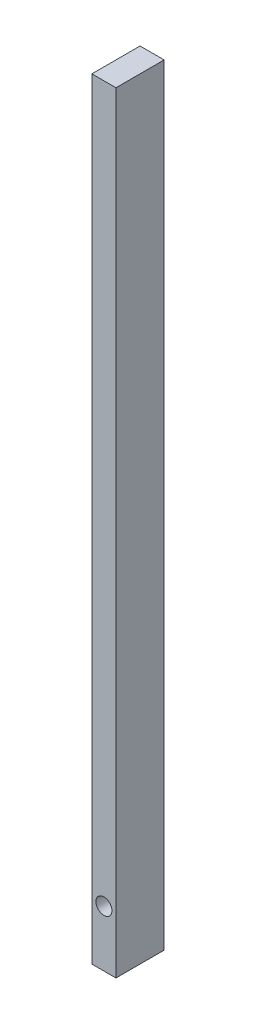
SolidWorks part; units mm, degrees
ref_plane "Front Plane" through (0, 0, 0) normal (0, 0, 1) x (1, 0, 0)
ref_plane "Top Plane" through (0, 0, 0) normal (0, 1, 0) x (1, 0, 0)
ref_plane "Right Plane" through (0, 0, 0) normal (1, 0, 0) x (0, 0, -1)
sketch "Sketch1" plane through (0, 0, 0) normal (1, 0, 0) x (0, 0, -1)
  line L1 (-19.05, 304.8) -> (19.05, 304.8)
  line L2 (-19.05, 304.8) -> (-19.05, -304.8)
  line L3 (-19.05, -304.8) -> (19.05, -304.8)
  line L4 (19.05, 304.8) -> (19.05, -304.8)
  line L5 (-19.05, 304.8) -> (19.05, -304.8) construction
  line L6 (-19.05, -304.8) -> (19.05, 304.8) construction
  point P0 (0, 0)
  dimension "D1" = 38.1
  dimension "D2" = 609.6
extrude "Boss-Extrude1" add sketch "Sketch1" along normal blind 19.05
sketch "Sketch2" plane through (0, 0, 19.05) normal (0, 0, 1) x (1, 0, 0)
  line L0 (9.525, -260.35) -> (9.525, -304.8) construction
  line L1 (19.05, -304.8) -> (0, -304.8) construction
  circle A0 centre (9.525, -260.35) radius 4.7625
  dimension "D2" = 9.525
  dimension "D1" = 44.45
extrude "Cut-Extrude1" cut sketch "Sketch2" against normal through all
sketch "Sketch3" plane through (0, 0, 19.05) normal (0, 0, 1) x (1, 0, 0)
  circle A0 centre (9.525, -260.35) radius 6.35
  dimension "D1" = 12.7
extrude "Cut-Extrude2" cut sketch "Sketch3" against normal blind 19.431
sketch "Sketch6" plane through (0, 0, -19.05) normal (0, 0, -1) x (-1, 0, 0)
  circle A0 centre (-9.525, -260.35) radius 12.319 construction
  circle A1 centre (-9.525, -248.031) radius 0.762
  point P5 (-9.525, -260.35)
  dimension "D1" = 24.638
  dimension "D2" = 1.524
extrude "Cut-Extrude5" cut sketch "Sketch6" against normal blind 12.7
